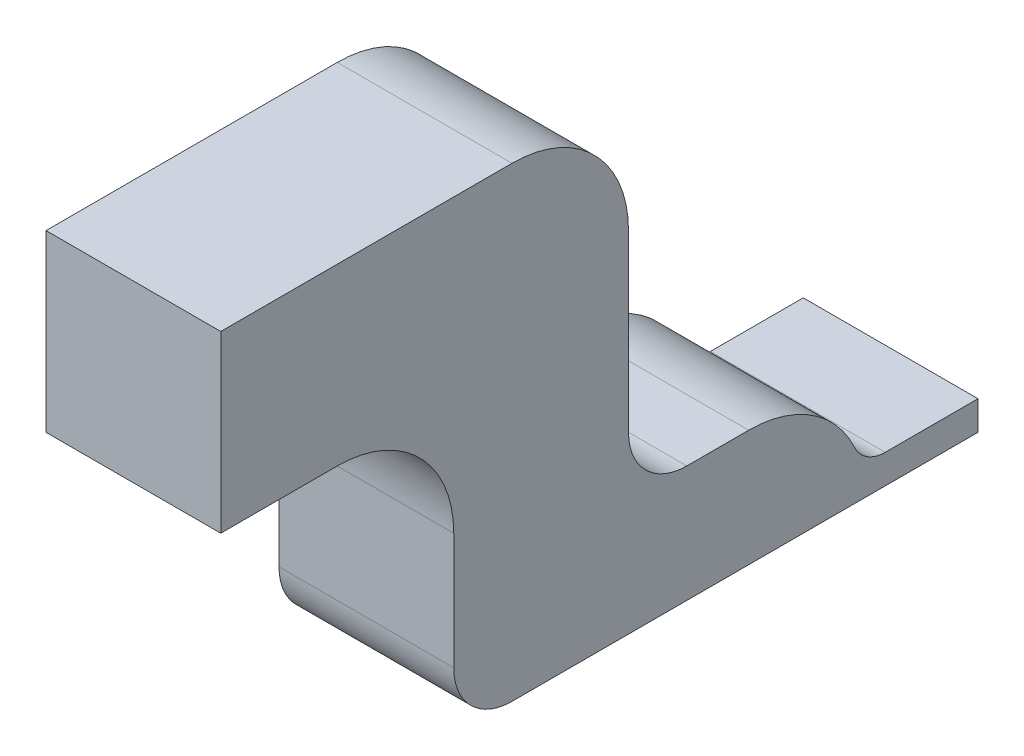
SolidWorks part; units mm, degrees
ref_plane "Plan de face" through (0, 0, 0) normal (0, 0, 1) x (1, 0, 0)
ref_plane "Plan de dessus" through (0, 0, 0) normal (0, 1, 0) x (1, 0, 0)
ref_plane "Plan de droite" through (0, 0, 0) normal (1, 0, 0) x (0, 0, -1)
sketch "Esquisse1" plane through (0, 0, 0) normal (0, 1, 0) x (1, 0, 0)
  line L1 (0, 0) -> (0.3, 0)
  line L2 (0, 0) -> (0, 0.7)
  line L3 (0, 0.7) -> (0.3, 0.7)
  line L4 (0.3, 0) -> (0.3, 0.7)
  dimension "D1" = 0.3
  dimension "D2" = 0.7
extrude "Boss.-Extru.1" add sketch "Esquisse1" along normal blind 0.2
sketch "Esquisse2" plane through (0, 0.2, 0) normal (0, 1, 0) x (1, 0, 0)
  line L0 (0.3, 0) -> (0.3, 0.7) construction
  line L1 (0, 0) -> (0.3, 0)
  line L2 (0, 0) -> (0, 0.3)
  line L3 (0, 0.3) -> (0.3, 0.3)
  line L4 (0.3, 0) -> (0.3, 0.3)
  dimension "D1" = 0.3
extrude "Boss.-Extru.2" add sketch "Esquisse2" along normal blind 0.6
sketch "Esquisse3" plane through (0, 0, 0) normal (0, 0, 1) x (1, 0, 0)
  line L0 (0.3, 0.8) -> (0.3, 0) construction
  line L1 (0, 0.8) -> (0.3, 0.8)
  line L2 (0, 0.8) -> (0, 0.5)
  line L3 (0, 0.5) -> (0.3, 0.5)
  line L4 (0.3, 0.8) -> (0.3, 0.5)
  dimension "D1" = 0.3
extrude "Boss.-Extru.3" add sketch "Esquisse3" along normal blind 0.4
fillet "Congé1" radius 0.2 2 edges at (0.15, 0.8, -0.3)
fillet "Congé2" radius 0.1 2 edges at (0.15, 0, 0)
sketch "Esquisse4" plane through (0, 0, -0.7) normal (0, 0, -1) x (-1, 0, 0)
  line L0 (0, 0.2) -> (0, 0) construction
  line L1 (-0.3, 0) -> (0, 0)
  line L2 (-0.3, 0) -> (-0.3, 0.05)
  line L3 (-0.3, 0.05) -> (0, 0.05)
  line L4 (0, 0) -> (0, 0.05)
  dimension "D1" = 0.05
extrude "Boss.-Extru.4" add sketch "Esquisse4" along normal blind 0.2
fillet "Congé6" radius 0.2 1 edges at (0.15, 0.2, -0.7)
fillet "Congé7" radius 0.058 1 edges
